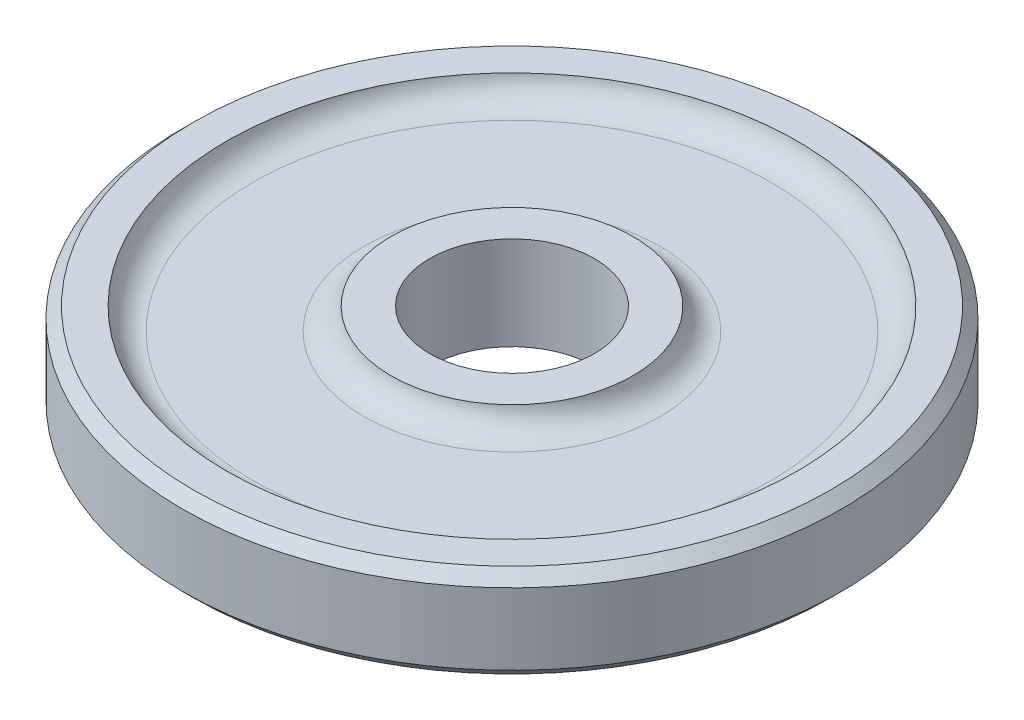
SolidWorks part; units mm, degrees
ref_plane "Front Plane" through (0, 0, 0) normal (0, 0, 1) x (1, 0, 0)
ref_plane "Top Plane" through (0, 0, 0) normal (0, 1, 0) x (1, 0, 0)
ref_plane "Right Plane" through (0, 0, 0) normal (1, 0, 0) x (0, 0, -1)
sketch "Sketch1" plane through (0, 0, 0) normal (0, 1, 0) x (1, 0, 0)
  circle A0 centre (0, 0) radius 60
  dimension "D1" = 120
extrude "Boss-Extrude1" add sketch "Sketch1" along normal blind 17
ref_plane "Plane1" through (0, 8.5, 0) normal (0, 1, 0) x (1, 0, 0)
sketch "Sketch2" plane through (0, 17, 0) normal (0, 1, 0) x (1, 0, 0)
  circle A0 centre (0, 0) radius 52
  circle A1 centre (0, 0) radius 22
  circle A2 centre (0, 0) radius 60 construction
  dimension "D1" = 8
  dimension "D2" = 30
extrude "Cut-Extrude1" cut sketch "Sketch2" against normal blind 4
mirror "Mirror1" about plane through (0, 8.5, 0) normal (0, 1, 0) of "Cut-Extrude1"
fillet "Fillet1" radius 5 4 edges at (0, 4, 52) (0, 4, 22) (0, 13, 22) (0, 13, 52)
chamfer "Chamfer1" distance 2 angle 45 2 edges at (0, 17, 60) (0, 0, 60)
sketch "Sketch3" plane through (0, 0, 0) normal (0, -1, 0) x (1, 0, 0)
  circle A0 centre (0, 0) radius 15
  dimension "D1" = 30
extrude "Cut-Extrude2" cut sketch "Sketch3" against normal through all
